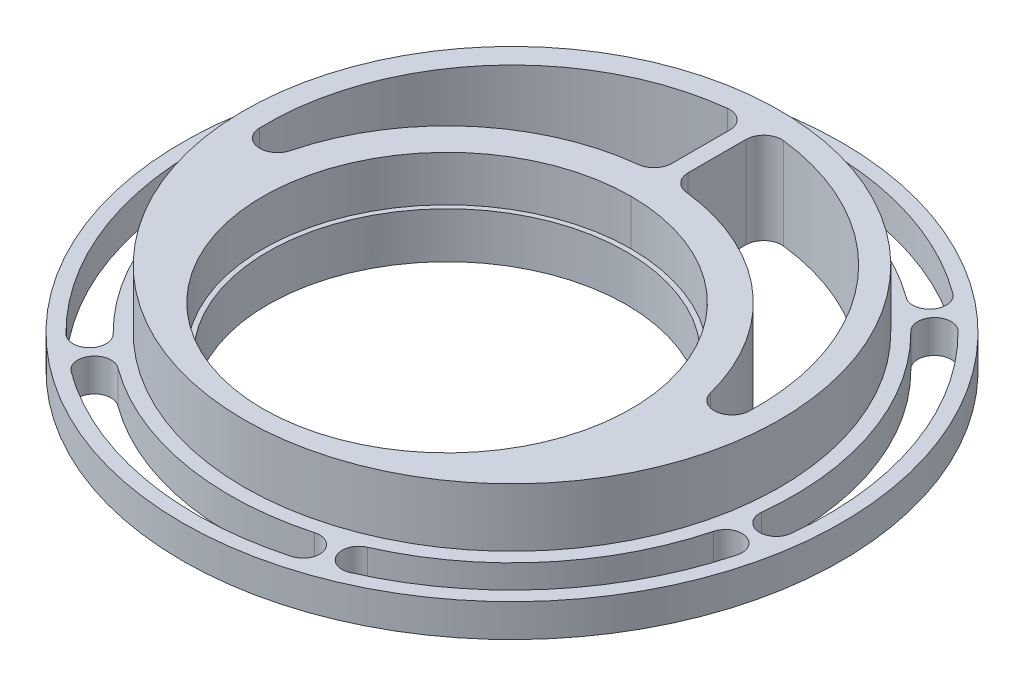
SolidWorks part; units mm, degrees
material "7075-T6, Plate (SS)"
ref_plane "X-Y Datum" through (0, 0, 0) normal (0, 0, 1) x (1, 0, 0)
ref_plane "X-Z Datum" through (0, 0, 0) normal (0, 1, 0) x (1, 0, 0)
ref_plane "Y-Z Datum" through (0, 0, 0) normal (1, 0, 0) x (0, 0, -1)
sketch "Sketch1" plane through (0, 0, 0) normal (0, 1, 0) x (1, 0, 0)
  line L0 (0, 0) -> (0, -12.7) construction
  line L1 (0, -43.0151) -> (0, 43.0151) construction
  line L2 (0, 61.9125) -> (0, 52.3875)
  circle A0 centre (0, -12.7) radius 35.052
  circle A1 centre (0, 0) radius 52.3875 construction
  circle A2 centre (0, 0) radius 57.15 construction
  circle A3 centre (0, 0) radius 61.9125
  point P12 (0, 57.15)
  dimension "D2" = 70.104
  dimension "D3" = 104.775
  dimension "D4" = 123.825
  dimension "D5" = 114.3
  dimension "D1" = 12.7
extrude "Boss-Extrude1" add sketch "Sketch1" along normal blind 4.5212 contours A3 A0 region at (-42.5405, 0, 42.5405)
sketch "Sketch3" plane through (0, 4.5212, 0) normal (0, 1, 0) x (1, 0, 0)
  circle A0 centre (0, 0) radius 52.3875 construction
  circle A1 centre (0, 0) radius 52.3875
extrude "Boss-Extrude2" add sketch "Sketch3" along normal blind 11.43
sketch "Sketch4" plane through (0, 0, 0) normal (0, -1, 0) x (1, 0, 0)
  circle A0 centre (0, 12.7) radius 35.052 construction
  circle A1 centre (0, 12.7) radius 35.052
extrude "Cut-Extrude1" cut sketch "Sketch4" against normal through all
sketch "Sketch9" plane through (0, 15.9512, 0) normal (0, 1, 0) x (1, 0, 0)
  circle A0 centre (0, -12.7) radius 35.052 construction
  circle A1 centre (0, -12.7) radius 35.052 construction
  circle A2 centre (0, -12.7) radius 36
  dimension "D1" = 72
extrude "Cut-Extrude3" cut sketch "Sketch9" against normal blind 8.89
ref_point "Point1"
ref_plane "Plane1" through (0, 0, 0) normal (1, 0, 0) x (0, 0, -1)
split line "Split Line1"
ref_plane "Plane2" through (0, 7.9756, 0) normal (0, 1, 0) x (1, 0, 0)
sketch "Sketch14" plane through (0, 7.9756, 0) normal (0, 1, 0) x (1, 0, 0)
  circle A0 centre (-33.2491, 22.3603) radius 8.255
ref_point "Point4"
sketch "Sketch10" plane through (0, 15.9512, 0) normal (0, 1, 0) x (1, 0, 0)
  circle A0 centre (0, 0) radius 52.3875 construction
  circle A1 centre (0, 0) radius 52.3875 construction
  arc A7 (0, -52.764) -> (0, 27.364) centre (0, -12.7) ccw
  arc A8 (0, 27.364) -> (0, -52.764) centre (0, -12.7) ccw
  arc A9 (0, -52.764) -> (0, 27.364) centre (0, -12.7) ccw construction
  arc A10 (0, 27.364) -> (0, -52.764) centre (0, -12.7) ccw construction
  circle A29 centre (0, 0) radius 48.3235 construction
  arc A30 (-30.6977, 13.0444) -> (30.6977, 13.0444) centre (0, -12.7) cw
  arc A31 (-43.3761, 21.2996) -> (43.3761, 21.2996) centre (0, 0) cw
  arc A34 (-30.6977, 13.0444) -> (-43.3761, 21.2996) centre (-36.5363, 17.9409) cw
  arc A35 (43.3761, 21.2996) -> (30.6977, 13.0444) centre (36.5363, 17.9409) cw
  dimension "D3" = 7.62
  dimension "D1" = 4.064
  dimension "D2" = 4.064
extrude "Cut-Extrude5" [suppressed] cut sketch "Sketch10" against normal through all contours A35 A31 A34 A30
sketch "Sketch15" [suppressed] plane through (0, 7.9756, 0) normal (0, 1, 0) x (1, 0, 0)
  line L1 (-2.1171, 31.2835) -> (-2.1171, 43.3958)
  line L4 (2.032, 31.291) -> (2.032, 43.4389)
  line L6 (-2.1764, 48.3235) -> (-2.1667, 48.2749) construction
  line L8 (2.1667, 48.2749) -> (2.1764, 48.3235) construction
  arc A0 (30.6977, 13.0444) -> (-30.6977, 13.0444) centre (0, -12.7) ccw construction
  arc A1 (30.6977, 13.0444) -> (-30.6977, 13.0444) centre (0, -12.7) ccw construction
  arc A2 (43.3761, 21.2996) -> (-43.3761, 21.2996) centre (0, 0) ccw construction
  arc A3 (-2.1171, 43.3958) -> (-6.9062, 47.8275) centre (-6.5621, 43.3958) ccw
  arc A4 (43.3761, 21.2996) -> (-43.3761, 21.2996) centre (0, 0) ccw construction
  arc A5 (6.5037, 47.8838) -> (2.032, 43.4389) centre (6.477, 43.4389) ccw
  arc A7 (-2.1171, 31.2835) -> (-5.362, 27.0036) centre (-6.5621, 31.2835) cw
  arc A9 (2.032, 31.291) -> (5.2509, 27.0184) centre (6.477, 31.291) ccw
  arc A10 (-6.9062, 47.8275) -> (6.5037, 47.8838) centre (0, 0) cw
  arc A11 (-5.362, 27.0036) -> (5.2509, 27.0184) centre (0, -12.7) cw
  point P9 (0, 37.4715)
  dimension "D1" = 4.445
  dimension "D2" = 2.1171
  dimension "D3" = 4.445
  dimension "D4" = 2.032
  dimension "D5" = 43.4389
  dimension "D6" = 31.2835
  dimension "D7" = 2.1171
  dimension "D8" = 12.148
  dimension "D9" = 12.1123
extrude "Boss-Extrude3" [suppressed] add sketch "Sketch15" along normal up to surface and the other way up to surface contours A9 L4 A5 A10 A3 L1 A7 A11
sketch "Sketch20" plane through (0, 4.5212, 0) normal (0, 1, 0) x (1, 0, 0)
  circle A0 centre (0, 0) radius 52.3875
  circle A2 centre (0, 0) radius 66.6087
sketch "Sketch25" [suppressed] plane through (0, 15.9512, 0) normal (0, 1, 0) x (1, 0, 0)
  line L6 (-4.6571, 31.2835) -> (-4.6571, 43.3958)
  line L7 (-4.6571, 31.2835) -> (-4.6571, 43.3958)
  line L12 (4.572, 43.4389) -> (4.572, 31.291)
  line L13 (4.572, 43.4389) -> (4.572, 31.291)
  circle A1 centre (-51.685, -7.6867) radius 0.134
  circle A2 centre (49.3335, -18.9489) radius 0.46
  arc A3 (48.8818, -18.8622) -> (48.9404, -18.71) centre (-0.2183, 0.1504) ccw
  arc A4 (48.8818, -18.8622) -> (48.9404, -18.71) centre (-0.2183, 0.1504) ccw
  arc A45 (-4.6571, 43.3958) -> (-6.6423, 45.2991) centre (-6.5621, 43.3958) ccw
  arc A46 (-5.9167, 29.4912) -> (-4.6571, 31.2835) centre (-6.5621, 31.2835) ccw
  arc A47 (-5.9167, 29.4912) -> (-32.6439, 14.6766) centre (0, -12.7) ccw
  arc A48 (-41.0962, 20.18) -> (-32.6439, 14.6766) centre (-36.5363, 17.9409) ccw
  arc A49 (-6.6423, 45.2991) -> (-41.0962, 20.18) centre (0, 0) ccw
  arc A50 (-4.6571, 43.3958) -> (-6.6423, 45.2991) centre (-6.5621, 43.3958) ccw
  arc A51 (-5.9167, 29.4912) -> (-4.6571, 31.2835) centre (-6.5621, 31.2835) ccw
  arc A52 (-5.9167, 29.4912) -> (-32.6439, 14.6766) centre (0, -12.7) ccw
  arc A53 (-41.0962, 20.18) -> (-32.6439, 14.6766) centre (-36.5363, 17.9409) ccw
  arc A54 (-6.6423, 45.2991) -> (-41.0962, 20.18) centre (0, 0) ccw
  circle A68 centre (-0.2183, 0.1504) radius 52.1224
  circle A69 centre (0, -12.7) radius 32.512
  circle A70 centre (0, -12.7) radius 32.512
  arc A72 (32.6439, 14.6766) -> (41.0962, 20.18) centre (36.5363, 17.9409) ccw
  arc A73 (4.572, 31.291) -> (5.8124, 29.5056) centre (6.477, 31.291) ccw
  arc A74 (32.6439, 14.6766) -> (5.8124, 29.5056) centre (0, -12.7) ccw
  arc A75 (41.0962, 20.18) -> (6.3564, 45.3401) centre (0, 0) ccw
  arc A76 (6.3564, 45.3401) -> (4.572, 43.4389) centre (6.477, 43.4389) ccw
  arc A77 (32.6439, 14.6766) -> (41.0962, 20.18) centre (36.5363, 17.9409) ccw
  arc A78 (4.572, 31.291) -> (5.8124, 29.5056) centre (6.477, 31.291) ccw
  arc A79 (32.6439, 14.6766) -> (5.8124, 29.5056) centre (0, -12.7) ccw
  arc A80 (41.0962, 20.18) -> (6.3564, 45.3401) centre (0, 0) ccw
  arc A81 (6.3564, 45.3401) -> (4.572, 43.4389) centre (6.477, 43.4389) ccw
  arc M3 (30.6977, 13.0444) -> (5.2509, 27.0184) centre (0, -12.7) ccw
  arc M4 (5.2509, 27.0184) -> (2.032, 31.291) centre (6.477, 31.291) cw
  line M5 (2.032, 31.291) -> (2.032, 43.4389)
  arc M6 (2.032, 43.4389) -> (6.5037, 47.8838) centre (6.477, 43.4389) cw
  arc M7 (6.5037, 47.8838) -> (43.3761, 21.2996) centre (0, 0) cw
  arc M8 (43.3761, 21.2996) -> (30.6977, 13.0444) centre (36.5363, 17.9409) cw
  arc M9 (-5.362, 27.0036) -> (-30.6977, 13.0444) centre (0, -12.7) ccw
  arc M10 (-30.6977, 13.0444) -> (-43.3761, 21.2996) centre (-36.5363, 17.9409) cw
  arc M11 (-43.3761, 21.2996) -> (-6.9062, 47.8275) centre (0, 0) cw
  arc M12 (-6.9062, 47.8275) -> (-2.1171, 43.3958) centre (-6.5621, 43.3958) cw
  line M13 (-2.1171, 43.3958) -> (-2.1171, 31.2835)
  arc M14 (-2.1171, 31.2835) -> (-5.362, 27.0036) centre (-6.5621, 31.2835) cw
  arc M15 (0, 23.3) -> (0, -48.7) centre (0, -12.7) cw
  arc M16 (0, -48.7) -> (0, 23.3) centre (0, -12.7) cw
  dimension "D1" = 2.54
  dimension "D2" = 2.54
  dimension "D3" = 2.54
extrude "Boss-Extrude5" [suppressed] add sketch "Sketch25" along normal blind 1.27 contours A54 A50 L7 A51 A52 A53 M9 M14 M13 M12 M11 M10 | A70 M15 M16 | A68 A1 M16 M15 M14 M9 M10 M11 M12 M13 M8 M3 M4 M5 M6 M7 | A81 A80 A77 A79 A78 L13 M3 M8 M7 M6 M5 M4
ref_axis "Axis1" [suppressed] through (0, 0, 0) along (0, 0, -1)
sketch "Sketch26" plane through (0, 4.5212, 0) normal (0, 1, 0) x (1, 0, 0)
  line L0 (0, 0) -> (-57.7152, 9.6181)
  line L1 (0, 0) -> (-38.741, -43.8484)
  arc A0 (-58.0713, 6.3737) -> (-41.0626, -41.5543) centre (0, 0) ccw construction
  arc A1 (-61.3157, 6.7298) -> (-43.3568, -43.8759) centre (0, 0) ccw
  arc A2 (-54.8269, 6.0176) -> (-38.7685, -39.2327) centre (0, 0) ccw
  arc A3 (-54.8269, 6.0176) -> (-61.3157, 6.7298) centre (-58.0713, 6.3737) ccw
  arc A4 (-43.3568, -43.8759) -> (-38.7685, -39.2327) centre (-41.0626, -41.5543) ccw
  point P4 (-55.0559, -19.5382)
  dimension "D2" = 3.2639
  dimension "D4" = 6.5278
  dimension "D1" = 58.42
  dimension "D3" = 58
extrude "Cut-Extrude6" cut sketch "Sketch26" against normal up to surface (4.5212 mm away) contours A2 A4 A1 A3 up to face at (0, 0, 47.752)
pattern_circular "CirPattern2" count 6 over 360 about axis through (0, 4.5212, 0) along (0, 1, 0) of "Cut-Extrude6"
sketch "Sketch27" plane through (0, 15.9512, 0) normal (0, 1, 0) x (1, 0, 0)
  line L0 (0, 0) -> (0, 50000) construction
  line L3 (-1.5875, 44.1588) -> (-1.5875, 32.8602)
  line L5 (1.5875, 44.1588) -> (1.5875, 32.8602)
  arc A9 (-41.0432, -2.2608) -> (-47.9187, -1.5099) centre (-44.428, -1.3999) cw
  arc A18 (-5.4791, 47.6284) -> (-47.9187, -1.5099) centre (0, 0) ccw
  arc A19 (-4.693, 29.3892) -> (-41.0432, -2.2608) centre (0, -12.7) ccw
  arc A20 (-5.4791, 47.6284) -> (-1.5875, 44.1588) centre (-5.08, 44.1588) cw
  arc A21 (-1.5875, 32.8602) -> (-4.693, 29.3892) centre (-5.08, 32.8602) cw
  arc A22 (1.5875, 32.8602) -> (4.693, 29.3892) centre (5.08, 32.8602) ccw
  arc A23 (5.4791, 47.6284) -> (1.5875, 44.1588) centre (5.08, 44.1588) ccw
  arc A24 (4.693, 29.3892) -> (41.0432, -2.2608) centre (0, -12.7) cw
  arc A25 (5.4791, 47.6284) -> (47.9187, -1.5099) centre (0, 0) cw
  arc A26 (41.0432, -2.2608) -> (47.9187, -1.5099) centre (44.428, -1.3999) ccw
  point P18 (-1.5875, 47.9162)
  point P22 (1.5875, 47.9162)
  dimension "D3" = 3.4925
  dimension "D2" = 3.4925
extrude "Cut-Extrude7" cut sketch "Sketch27" against normal through all both and the other way through all
ref_point "Point6"
sketch "Sketch28" plane through (0, 0, 0) normal (0, -1, 0) x (1, 0, 0)
  line L1 (1.5875, -32.8602) -> (1.5875, -44.1588)
  line L2 (1.5875, -32.8602) -> (1.5875, -44.1588)
  line L3 (-1.5875, -44.1588) -> (-1.5875, -32.8602)
  line L4 (-1.5875, -44.1588) -> (-1.5875, -32.8602)
  circle A6 centre (0, 12.7) radius 35.052
  circle A7 centre (0, 12.7) radius 35.052
  arc A11 (-38.7685, 39.2327) -> (-54.8269, -6.0176) centre (0, 0) ccw
  arc A12 (-61.3157, -6.7298) -> (-54.8269, -6.0176) centre (-58.0713, -6.3737) ccw
  arc A13 (-43.3568, 43.8759) -> (-61.3157, -6.7298) centre (0, 0) ccw
  arc A14 (-38.7685, 39.2327) -> (-43.3568, 43.8759) centre (-41.0626, 41.5543) ccw
  arc A15 (-38.7685, 39.2327) -> (-54.8269, -6.0176) centre (0, 0) ccw
  arc A16 (-61.3157, -6.7298) -> (-54.8269, -6.0176) centre (-58.0713, -6.3737) ccw
  arc A17 (-43.3568, 43.8759) -> (-61.3157, -6.7298) centre (0, 0) ccw
  arc A18 (-38.7685, 39.2327) -> (-43.3568, 43.8759) centre (-41.0626, 41.5543) ccw
  arc A19 (14.5923, 53.1908) -> (-32.6248, 44.4727) centre (0, 0) ccw
  arc A20 (-36.486, 49.7361) -> (-32.6248, 44.4727) centre (-34.5554, 47.1044) ccw
  arc A21 (16.3193, 59.486) -> (-36.486, 49.7361) centre (0, 0) ccw
  arc A22 (14.5923, 53.1908) -> (16.3193, 59.486) centre (15.4558, 56.3384) ccw
  arc A23 (14.5923, 53.1908) -> (-32.6248, 44.4727) centre (0, 0) ccw
  arc A24 (-36.486, 49.7361) -> (-32.6248, 44.4727) centre (-34.5554, 47.1044) ccw
  arc A25 (16.3193, 59.486) -> (-36.486, 49.7361) centre (0, 0) ccw
  arc A26 (14.5923, 53.1908) -> (16.3193, 59.486) centre (15.4558, 56.3384) ccw
  arc A27 (-53.3607, -13.9581) -> (-22.2021, -50.4902) centre (0, 0) ccw
  arc A28 (-24.8297, -56.4658) -> (-22.2021, -50.4902) centre (-23.5159, -53.478) ccw
  arc A29 (-59.676, -15.6101) -> (-24.8297, -56.4658) centre (0, 0) ccw
  arc A30 (-53.3607, -13.9581) -> (-59.676, -15.6101) centre (-56.5184, -14.7841) ccw
  arc A31 (-53.3607, -13.9581) -> (-22.2021, -50.4902) centre (0, 0) ccw
  arc A32 (-24.8297, -56.4658) -> (-22.2021, -50.4902) centre (-23.5159, -53.478) ccw
  arc A33 (-59.676, -15.6101) -> (-24.8297, -56.4658) centre (0, 0) ccw
  arc A34 (-53.3607, -13.9581) -> (-59.676, -15.6101) centre (-56.5184, -14.7841) ccw
  arc A35 (-14.5923, -53.1908) -> (32.6248, -44.4727) centre (0, 0) ccw
  arc A36 (36.486, -49.7361) -> (32.6248, -44.4727) centre (34.5554, -47.1044) ccw
  arc A37 (-16.3193, -59.486) -> (36.486, -49.7361) centre (0, 0) ccw
  arc A38 (-14.5923, -53.1908) -> (-16.3193, -59.486) centre (-15.4558, -56.3384) ccw
  arc A39 (-14.5923, -53.1908) -> (32.6248, -44.4727) centre (0, 0) ccw
  arc A40 (36.486, -49.7361) -> (32.6248, -44.4727) centre (34.5554, -47.1044) ccw
  arc A41 (-16.3193, -59.486) -> (36.486, -49.7361) centre (0, 0) ccw
  arc A42 (-14.5923, -53.1908) -> (-16.3193, -59.486) centre (-15.4558, -56.3384) ccw
  arc A43 (38.7685, -39.2327) -> (54.8269, 6.0176) centre (0, 0) ccw
  arc A44 (61.3157, 6.7298) -> (54.8269, 6.0176) centre (58.0713, 6.3737) ccw
  arc A45 (43.3568, -43.8759) -> (61.3157, 6.7298) centre (0, 0) ccw
  arc A46 (38.7685, -39.2327) -> (43.3568, -43.8759) centre (41.0626, -41.5543) ccw
  arc A47 (38.7685, -39.2327) -> (54.8269, 6.0176) centre (0, 0) ccw
  arc A48 (61.3157, 6.7298) -> (54.8269, 6.0176) centre (58.0713, 6.3737) ccw
  arc A49 (43.3568, -43.8759) -> (61.3157, 6.7298) centre (0, 0) ccw
  arc A50 (38.7685, -39.2327) -> (43.3568, -43.8759) centre (41.0626, -41.5543) ccw
  arc A51 (53.3607, 13.9581) -> (22.2021, 50.4902) centre (0, 0) ccw
  arc A52 (24.8297, 56.4658) -> (22.2021, 50.4902) centre (23.5159, 53.478) ccw
  arc A53 (59.676, 15.6101) -> (24.8297, 56.4658) centre (0, 0) ccw
  arc A54 (53.3607, 13.9581) -> (59.676, 15.6101) centre (56.5184, 14.7841) ccw
  arc A55 (53.3607, 13.9581) -> (22.2021, 50.4902) centre (0, 0) ccw
  arc A56 (24.8297, 56.4658) -> (22.2021, 50.4902) centre (23.5159, 53.478) ccw
  arc A57 (59.676, 15.6101) -> (24.8297, 56.4658) centre (0, 0) ccw
  arc A58 (53.3607, 13.9581) -> (59.676, 15.6101) centre (56.5184, 14.7841) ccw
  arc A60 (4.693, -29.3892) -> (1.5875, -32.8602) centre (5.08, -32.8602) ccw
  arc A61 (4.693, -29.3892) -> (41.0432, 2.2608) centre (0, 12.7) ccw
  arc A62 (47.9187, 1.5099) -> (41.0432, 2.2608) centre (44.428, 1.3999) ccw
  arc A63 (5.4791, -47.6284) -> (47.9187, 1.5099) centre (0, 0) ccw
  arc A64 (1.5875, -44.1588) -> (5.4791, -47.6284) centre (5.08, -44.1588) ccw
  arc A65 (4.693, -29.3892) -> (1.5875, -32.8602) centre (5.08, -32.8602) ccw
  arc A66 (4.693, -29.3892) -> (41.0432, 2.2608) centre (0, 12.7) ccw
  arc A67 (47.9187, 1.5099) -> (41.0432, 2.2608) centre (44.428, 1.3999) ccw
  arc A68 (5.4791, -47.6284) -> (47.9187, 1.5099) centre (0, 0) ccw
  arc A69 (1.5875, -44.1588) -> (5.4791, -47.6284) centre (5.08, -44.1588) ccw
  arc A70 (-5.4791, -47.6284) -> (-1.5875, -44.1588) centre (-5.08, -44.1588) ccw
  arc A71 (-47.9187, 1.5099) -> (-5.4791, -47.6284) centre (0, 0) ccw
  arc A72 (-41.0432, 2.2608) -> (-47.9187, 1.5099) centre (-44.428, 1.3999) ccw
  arc A73 (-41.0432, 2.2608) -> (-4.693, -29.3892) centre (0, 12.7) ccw
  arc A74 (-1.5875, -32.8602) -> (-4.693, -29.3892) centre (-5.08, -32.8602) ccw
  arc A75 (-5.4791, -47.6284) -> (-1.5875, -44.1588) centre (-5.08, -44.1588) ccw
  arc A76 (-47.9187, 1.5099) -> (-5.4791, -47.6284) centre (0, 0) ccw
  arc A77 (-41.0432, 2.2608) -> (-47.9187, 1.5099) centre (-44.428, 1.3999) ccw
  arc A78 (-41.0432, 2.2608) -> (-4.693, -29.3892) centre (0, 12.7) ccw
  arc A79 (-1.5875, -32.8602) -> (-4.693, -29.3892) centre (-5.08, -32.8602) ccw
  arc M39 (53.3607, 13.9581) -> (22.2021, 50.4902) centre (0, 0) ccw
  arc M40 (22.2021, 50.4902) -> (24.8297, 56.4658) centre (23.5159, 53.478) cw
  arc M41 (24.8297, 56.4658) -> (59.676, 15.6101) centre (0, 0) cw
  arc M42 (59.676, 15.6101) -> (53.3607, 13.9581) centre (56.5184, 14.7841) cw
  arc M43 (38.7685, -39.2327) -> (54.8269, 6.0176) centre (0, 0) ccw
  arc M44 (54.8269, 6.0176) -> (61.3157, 6.7298) centre (58.0713, 6.3737) cw
  arc M45 (61.3157, 6.7298) -> (43.3568, -43.8759) centre (0, 0) cw
  arc M46 (43.3568, -43.8759) -> (38.7685, -39.2327) centre (41.0626, -41.5543) cw
  arc M47 (-14.5923, -53.1908) -> (32.6248, -44.4727) centre (0, 0) ccw
  arc M48 (32.6248, -44.4727) -> (36.486, -49.7361) centre (34.5554, -47.1044) cw
  arc M49 (36.486, -49.7361) -> (-16.3193, -59.486) centre (0, 0) cw
  arc M50 (-16.3193, -59.486) -> (-14.5923, -53.1908) centre (-15.4558, -56.3384) cw
  arc M51 (-53.3607, -13.9581) -> (-22.2021, -50.4902) centre (0, 0) ccw
  arc M52 (-22.2021, -50.4902) -> (-24.8297, -56.4658) centre (-23.5159, -53.478) cw
  arc M53 (-24.8297, -56.4658) -> (-59.676, -15.6101) centre (0, 0) cw
  arc M54 (-59.676, -15.6101) -> (-53.3607, -13.9581) centre (-56.5184, -14.7841) cw
  arc M55 (14.5923, 53.1908) -> (-32.6248, 44.4727) centre (0, 0) ccw
  arc M56 (-32.6248, 44.4727) -> (-36.486, 49.7361) centre (-34.5554, 47.1044) cw
  arc M57 (-36.486, 49.7361) -> (16.3193, 59.486) centre (0, 0) cw
  arc M58 (16.3193, 59.486) -> (14.5923, 53.1908) centre (15.4558, 56.3384) cw
  arc M59 (-38.7685, 39.2327) -> (-54.8269, -6.0176) centre (0, 0) ccw
  arc M60 (-54.8269, -6.0176) -> (-61.3157, -6.7298) centre (-58.0713, -6.3737) cw
  arc M61 (-61.3157, -6.7298) -> (-43.3568, 43.8759) centre (0, 0) cw
  arc M62 (-43.3568, 43.8759) -> (-38.7685, 39.2327) centre (-41.0626, 41.5543) cw
  circle M63 centre (0, 12.7) radius 35.052
  circle M64 centre (0, 0) radius 61.9125
  line M65 (1.5875, -44.1588) -> (1.5875, -32.8602)
  arc M66 (1.5875, -32.8602) -> (4.693, -29.3892) centre (5.08, -32.8602) cw
  arc M67 (4.693, -29.3892) -> (41.0432, 2.2608) centre (0, 12.7) ccw
  arc M68 (41.0432, 2.2608) -> (47.9187, 1.5099) centre (44.428, 1.3999) cw
  arc M69 (47.9187, 1.5099) -> (5.4791, -47.6284) centre (0, 0) cw
  arc M70 (5.4791, -47.6284) -> (1.5875, -44.1588) centre (5.08, -44.1588) cw
  line M71 (-1.5875, -32.8602) -> (-1.5875, -44.1588)
  arc M72 (-1.5875, -44.1588) -> (-5.4791, -47.6284) centre (-5.08, -44.1588) cw
  arc M73 (-5.4791, -47.6284) -> (-47.9187, 1.5099) centre (0, 0) cw
  arc M74 (-47.9187, 1.5099) -> (-41.0432, 2.2608) centre (-44.428, 1.3999) cw
  arc M75 (-41.0432, 2.2608) -> (-4.693, -29.3892) centre (0, 12.7) ccw
  arc M76 (-4.693, -29.3892) -> (-1.5875, -32.8602) centre (-5.08, -32.8602) cw
  dimension "D1" = 0
  dimension "D2" = 0
  dimension "D3" = 0
  dimension "D4" = 0
  dimension "D5" = 0
  dimension "D6" = 0
  dimension "D7" = 0
  dimension "D8" = 0
  dimension "D9" = 0
extrude "Boss-Extrude6" add sketch "Sketch28" along normal blind 1.905 contours M64 M76 M71 M72 M73 M74 M75 M70 M65 M66 M67 M68 M69 M63 M62 M59 M60 M61 M58 M55 M56 M57 M54 M51 M52 M53 M50 M47 M48 M49 M46 M43 M44 M45 M42 M39 M40 M41 region at (-61.7374, 0, 0)
sketch "Sketch29" plane through (0, 4.5212, 0) normal (0, 1, 0) x (1, 0, 0)
  circle A0 centre (0, 0) radius 61.9125
  circle A1 centre (0, 0) radius 64.4525
  dimension "D1" = 123.825
  dimension "D2" = 2.54
extrude "Boss-Extrude7" add sketch "Sketch29" against normal through all
equation "\"NumSlots\"= 3"
equation "\"SlotAngSpacing\"= 4deg"
equation "\"SlotAngDim\"= 360deg / \"NumSlots\""
equation "\"SlotDim\"= \"SlotAngDim\" - \"SlotAngSpacing\""
equation "\"CutoutEndRad\"= .3in"
equation "\"Slot_Length\"= 4 in"
